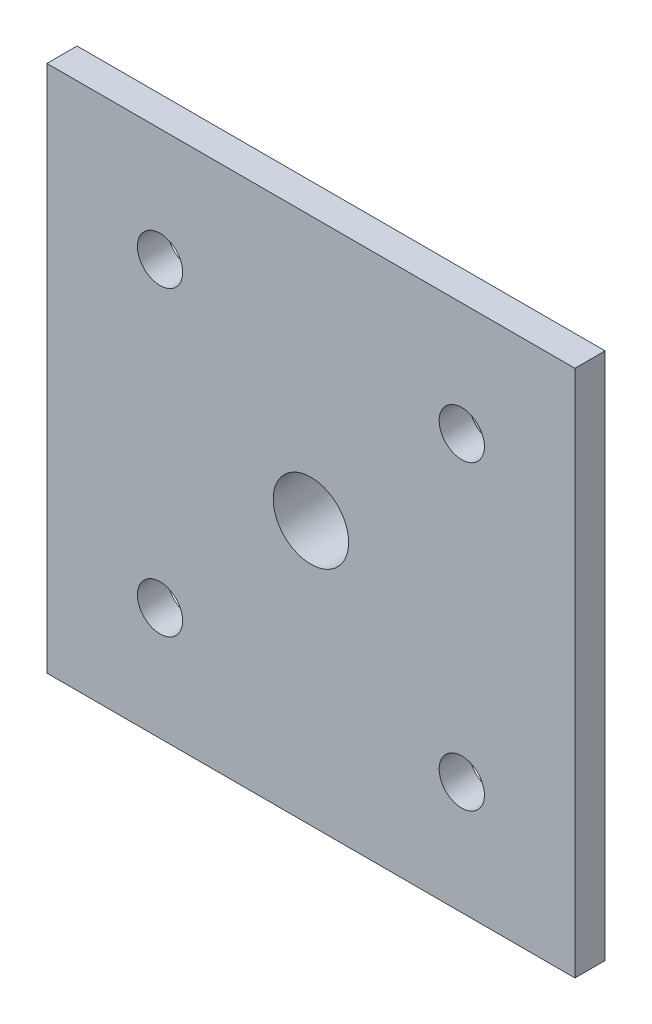
SolidWorks part; units mm, degrees
material "6061 Alloy"
ref_plane "Front Plane" through (0, 0, 0) normal (0, 0, 1) x (1, 0, 0)
ref_plane "Top Plane" through (0, 0, 0) normal (0, 1, 0) x (1, 0, 0)
ref_plane "Right Plane" through (0, 0, 0) normal (1, 0, 0) x (0, 0, -1)
sketch "Sketch1" plane through (0, 0, 0) normal (0, 0, 1) x (1, 0, 0)
  line L1 (-17.5, 17.5) -> (17.5, 17.5)
  line L2 (-17.5, 17.5) -> (-17.5, -17.5)
  line L3 (-17.5, -17.5) -> (17.5, -17.5)
  line L4 (17.5, 17.5) -> (17.5, -17.5)
  line L5 (-17.5, 17.5) -> (17.5, -17.5) construction
  line L6 (-17.5, -17.5) -> (17.5, 17.5) construction
  point P0 (0, 0)
  dimension "D1" = 35
  dimension "D2" = 35
extrude "Boss-Extrude1" add sketch "Sketch1" along normal blind 2
sketch "Sketch2" plane through (0, 0, 2) normal (0, 0, 1) x (1, 0, 0)
  line L1 (-10, 10) -> (10, 10) construction
  line L2 (-10, 10) -> (-10, -10) construction
  line L3 (-10, -10) -> (10, -10) construction
  line L4 (10, 10) -> (10, -10) construction
  line L5 (-10, 10) -> (10, -10) construction
  line L6 (-10, -10) -> (10, 10) construction
  circle A0 centre (0, 0) radius 2.5
  circle A1 centre (-10, 10) radius 1.5
  circle A2 centre (10, 10) radius 1.5
  circle A3 centre (10, -10) radius 1.5
  circle A4 centre (-10, -10) radius 1.5
  dimension "D1" = 3
  dimension "D2" = 5
  dimension "D3" = 20
  dimension "D4" = 20
extrude "Cut-Extrude1" cut sketch "Sketch2" against normal blind 3
sketch "Sketch3" plane through (0, 0, 0) normal (0, 0, -1) x (-1, 0, 0)
  circle A0 centre (0, 0) radius 2.5
  circle A1 centre (0, 0) radius 7.5
  dimension "D1" = 5
  dimension "D2" = 15
extrude "Boss-Extrude2" add sketch "Sketch3" along normal blind 5
